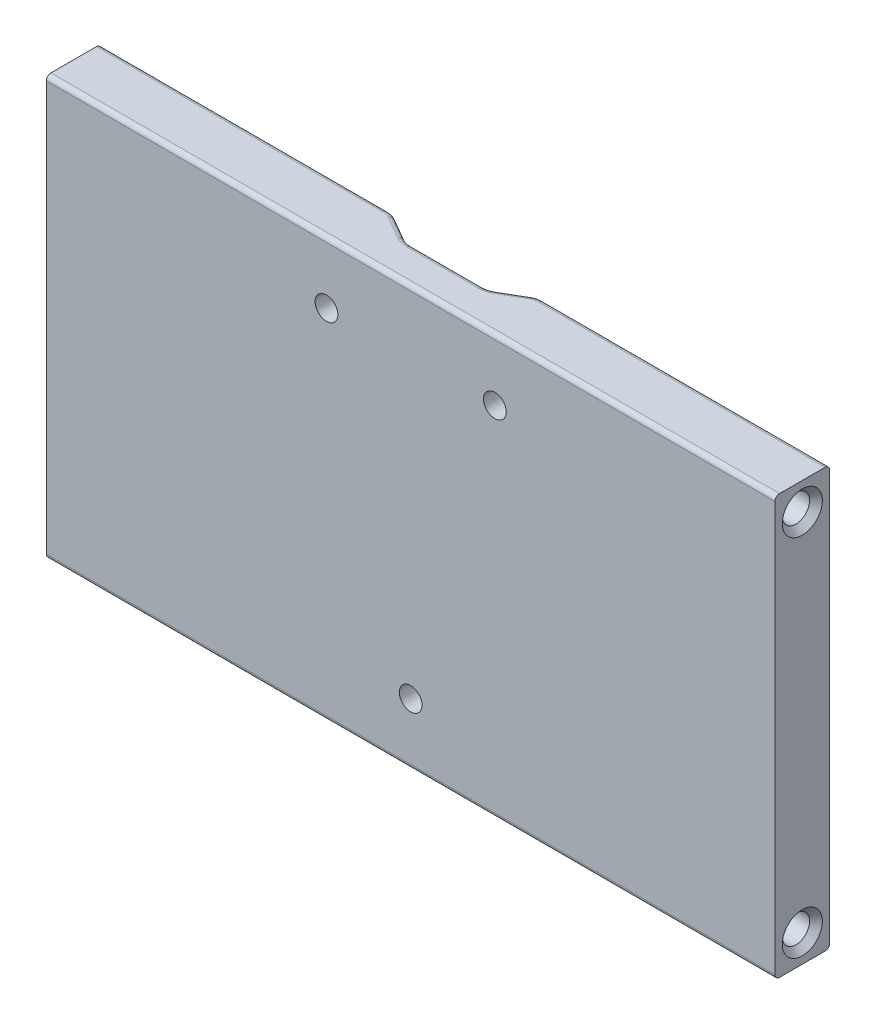
SolidWorks part; units mm, degrees
material "ABS"
ref_plane "Ebene vorne" through (0, 0, 0) normal (0, 0, 1) x (1, 0, 0)
ref_plane "Ebene oben" through (0, 0, 0) normal (0, 1, 0) x (1, 0, 0)
ref_plane "Ebene rechts" through (0, 0, 0) normal (1, 0, 0) x (0, 0, -1)
sketch "Skizze1" plane through (0, 0, 0) normal (0, 0, 1) x (1, 0, 0)
  line L0 (0, 50.7625) -> (0, -50.1476) construction
  line L1 (-61.9688, 0) -> (71.1622, 0) construction
  line L2 (-40, -23) -> (-40, 23)
  line L3 (-40, 23) -> (40, 23)
  line L4 (40, -23) -> (40, 23)
  line L5 (-40, -23) -> (40, -23)
  point P9 (0, 23)
  point P10 (0, -23)
  point P12 (40, 0)
  point P13 (-40, 0)
  dimension "D1" = 80
  dimension "D2" = 46
extrude "Aufsatz-Linear austragen1" add sketch "Skizze1" along normal blind 3 and the other way blind 3
hole_wizard "Ø3.0 (3) Durchmesser Bohrung1" positions "Skizze3" profile "Skizze2" hole size "Ø3.0" standard "ANSI Metrisch"
sketch "Skizze3" plane through (40, 0, 0) normal (1, 0, 0) x (0, 0, -1)
  line L0 (0, -57.6805) -> (0, 49.3664) construction
  line L3 (-29.0599, 0) -> (25.5739, 0) construction
  point P0 (0, -20)
  point P14 (0, 20)
  dimension "D1" = 40
sketch "Skizze2" plane through (40, -20, 0) normal (0, 1, 0) x (0, 0, -1)
  line L0 (0, 0) -> (0, 10.9013)
  line L1 (0, 10.9013) -> (1.5, 10)
  line L2 (1.5, 10) -> (1.5, 0)
  line L5 (1.5, 0) -> (0, 0)
  line L10 (0, 10.9013) -> (-1.5, 10) construction
  line L11 (0, -6.35) -> (0, 107.95) construction
  dimension "Bohrerdurchmesser" = 3
  dimension "Bohrungstiefe" = 10
  dimension "Spitzenwinkel" = 118
mirror "Spiegeln1" about plane through (0, 0, 0) normal (1, 0, 0) of "Ø3.0 (3) Durchmesser Bohrung1"
sketch "Skizze4" plane through (0, 0, -3) normal (0, 0, 1) x (1, 0, 0)
  line L0 (-60.4279, 0) -> (54.1706, 0) construction
  line L1 (0, 30.4132) -> (0, -30.8408) construction
  line L2 (-15, -21.5) -> (-15, 21.5)
  line L3 (-15, 21.5) -> (15, 21.5)
  line L4 (15, -21.5) -> (15, 21.5)
  line L5 (-15, -21.5) -> (15, -21.5)
  point P9 (0, 21.5)
  point P10 (0, -21.5)
  point P12 (15, 0)
  point P13 (-15, 0)
  dimension "D1" = 43
  dimension "D2" = 30
extrude "Schnitt-Linear austragen1" cut sketch "Skizze4" along normal blind 3
fillet "Verrundung1" radius 3 4 edges at (-15, -21.5, -1.5) (15, -21.5, -1.5) (-15, 21.5, -1.5) (15, 21.5, -1.5)
sketch "Skizze5" plane through (0, 0, 0) normal (0, 0, 1) x (1, 0, 0)
  line L0 (0, 37.6648) -> (0, -30.8674) construction
  line L1 (48.5186, 0) -> (-42.7578, 0) construction
  line L2 (37, -14.5) -> (37, 14.5)
  line L3 (34, 17.5) -> (21, 17.5)
  line L4 (18, 14.5) -> (18, -14.5)
  line L5 (34, -17.5) -> (21, -17.5)
  line L6 (-34, -17.5) -> (-21, -17.5)
  line L7 (-18, 14.5) -> (-18, -14.5)
  line L8 (-34, 17.5) -> (-21, 17.5)
  line L9 (-37, -14.5) -> (-37, 14.5)
  arc A0 (-18, 14.5) -> (-21, 17.5) centre (-21, 14.5) ccw
  arc A1 (-34, 17.5) -> (-37, 14.5) centre (-34, 14.5) ccw
  arc A2 (-37, -14.5) -> (-34, -17.5) centre (-34, -14.5) ccw
  arc A3 (-21, -17.5) -> (-18, -14.5) centre (-21, -14.5) ccw
  arc A4 (34, -17.5) -> (37, -14.5) centre (34, -14.5) ccw
  arc A5 (21, -17.5) -> (18, -14.5) centre (21, -14.5) cw
  arc A6 (18, 14.5) -> (21, 17.5) centre (21, 14.5) cw
  arc A7 (37, 14.5) -> (34, 17.5) centre (34, 14.5) ccw
  point P5 (-37, 0)
  point P10 (18, 0)
  point P11 (37, 0)
  point P12 (-18, 0)
  point P19 (-18, 17.5)
  point P22 (-37, 17.5)
  point P25 (-37, -17.5)
  point P28 (-18, -17.5)
  point P31 (37, -17.5)
  point P34 (18, -17.5)
  point P37 (18, 17.5)
  point P40 (37, 17.5)
  dimension "D1" = 3
  dimension "D2" = 35
  dimension "D3" = 74
  dimension "D4" = 36
extrude "Schnitt-Linear austragen2" cut sketch "Skizze5" against normal through all and the other way blind 1.5
sketch "Skizze8" plane through (0, 0, 0) normal (0, 0, -1) x (-1, 0, 0)
  line L0 (0, -37.8459) -> (0, 37.4434) construction
  line L1 (-53.7919, 0) -> (48.3384, 0) construction
  line L2 (26.4757, 16.255) -> (-18.8183, 16.255) construction
  circle A0 centre (0, -16.255) radius 1.25
  circle A1 centre (9.245, 16.255) radius 1.25
  circle A2 centre (-9.245, 16.255) radius 1.25
  dimension "D1" = 18.49
  dimension "D3" = 2.5
  dimension "D2" = 32.51
  dimension "D4" = 16.255
extrude "Schnitt-Linear austragen4" cut sketch "Skizze8" against normal through all
sketch "Skizze9" plane through (0, 0, 0) normal (0, 1, 0) x (1, 0, 0)
  line L0 (0, 25.0981) -> (0, -21.3044) construction
  line L1 (-45.9333, 0) -> (46.4766, 0) construction
  line L2 (7.9641, 3) -> (-7.9641, 3)
  line L3 (-7.9641, 3) -> (-4.5, 1)
  line L4 (-4.5, 1) -> (4.5, 1)
  line L5 (40, 3) -> (-40, 3) construction
  line L6 (7.9641, 3) -> (4.5, 1)
  point P13 (0, 1)
  point P14 (0, 3)
  dimension "D1" = 2
  dimension "D2" = 9
  dimension "D3" = 30
extrude "Schnitt-Linear austragen5" cut sketch "Skizze9" along normal through all
fillet "Verrundung3" radius 2 4 edges at (7.9641, 22.25, -3) (-7.9641, 22.25, -3) (4.5, 22.25, -1) (-4.5, 22.25, -1)
fillet "Verrundung2" radius 0.5 68 edges at (18.8787, 16.6213, 1.5) (27.5, 17.5, 1.5) (36.1213, 16.6213, 1.5) (37, 0, 1.5) (36.1213, -16.6213, 1.5) (27.5, -17.5, 1.5) (18.8787, -16.6213, 1.5) (-14.1213, 20.6213, 0) (0, 21.5, 0) (14.1213, 20.6213, 0) (15, 0, 0) (14.1213, -20.6213, 0) (0, -21.5, 0) (-14.1213, -20.6213, 0) (-36.1213, 16.6213, 1.5) (-27.5, 17.5, 1.5) (-18.8787, 16.6213, 1.5) (-18, 0, 1.5) (-18.8787, -16.6213, 1.5) (-27.5, -17.5, 1.5) (-36.1213, -16.6213, 1.5) (-18.8787, -16.6213, -3) (-27.5, -17.5, -3) (-36.1213, -16.6213, -3) (-37, 0, -3) (-36.1213, 16.6213, -3) (-27.5, 17.5, -3) (-18.8787, 16.6213, -3) (0, -21.5, -3) (-14.1213, -20.6213, -3) (-15, 0, -3) (-14.1213, 20.6213, -3) (10.25, 21.5, -3) (-10.25, 21.5, -3) (14.1213, 20.6213, -3) (15, 0, -3) (18.8787, -16.6213, -3) (18, 0, -3) (18.8787, 16.6213, -3) (27.5, 17.5, -3) (36.1213, 16.6213, -3) (37, 0, -3) (36.1213, -16.6213, -3) (18, 0, 1.5) (-15, 0, 0) (-37, 0, 1.5) (-18, 0, -3) (14.1213, -20.6213, -3) (27.5, -17.5, -3) (0, -23, 3) (0, -23, -3) (0, 23, 3) (24.25, 23, -3) (-24.25, 23, -3) (-7.9824, 21.5, -2.9319) (-6.2321, 21.5, -2) (-4.4817, 21.5, -1.0681) (0, 21.5, -1) (4.4817, 21.5, -1.0681) (6.2321, 21.5, -2) (7.9824, 21.5, -2.9319) (-7.9824, 23, -2.9319) (-6.2321, 23, -2) (-4.4817, 23, -1.0681) (0, 23, -1) (4.4817, 23, -1.0681) (6.2321, 23, -2) (7.9824, 23, -2.9319)
chamfer "Fase1" distance 0.7 angle 45 4 edges at (-40, 20, 1.5) (-40, -20, 1.5) (40, -20, -1.5) (40, 20, -1.5)
ref_axis "Achse1" through (-44, 0, 0) along (1, 0, 0)
ref_axis "Achse2" through (0, 0, -3.3) along (0, 0, 1)
ref_axis "Achse3" through (0, 25.3, 0) along (0, -1, 0)
